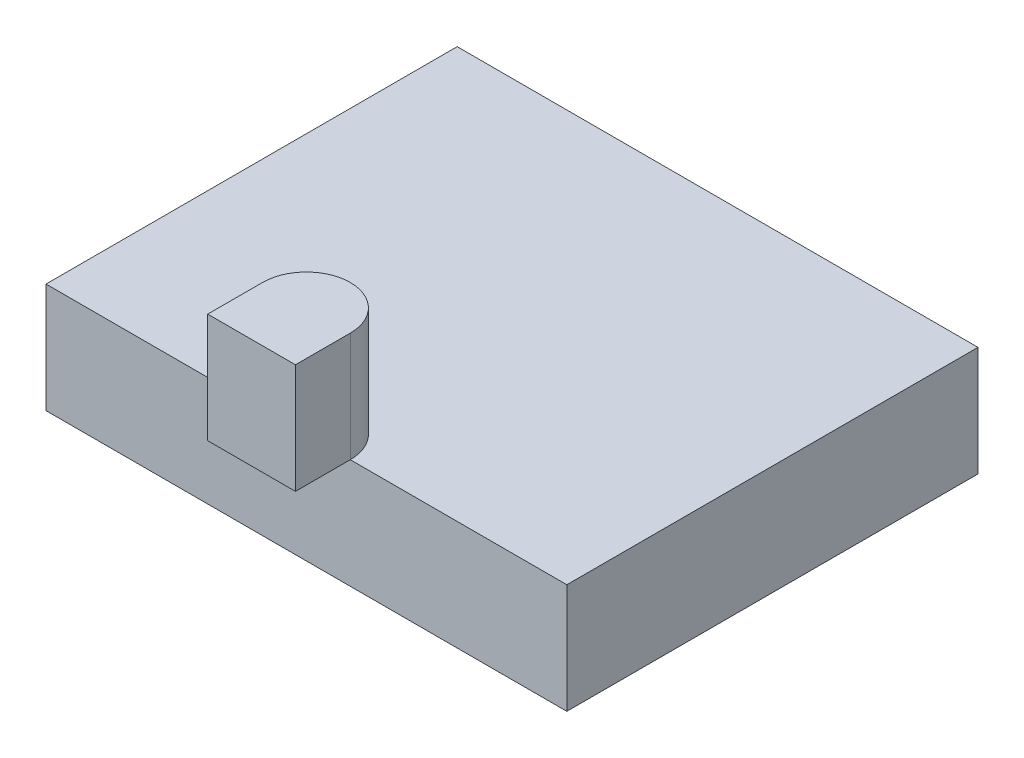
SolidWorks part; units mm, degrees
ref_plane "Front Plane" through (0, 0, 0) normal (0, 0, 1) x (1, 0, 0)
ref_plane "Top Plane" through (0, 0, 0) normal (0, 1, 0) x (1, 0, 0)
ref_plane "Right Plane" through (0, 0, 0) normal (1, 0, 0) x (0, 0, -1)
sketch "Sketch1" plane through (0, 0, 0) normal (0, 1, 0) x (1, 0, 0)
  line L1 (-47.5, 37.5) -> (47.5, 37.5)
  line L2 (-47.5, 37.5) -> (-47.5, -37.5)
  line L3 (-47.5, -37.5) -> (47.5, -37.5)
  line L4 (47.5, 37.5) -> (47.5, -37.5)
  line L5 (-47.5, 37.5) -> (47.5, -37.5) construction
  line L6 (-47.5, -37.5) -> (47.5, 37.5) construction
  point P0 (0, 0)
  dimension "D1" = 95
  dimension "D2" = 75
extrude "Boss-Extrude1" add sketch "Sketch1" along normal mid plane 20
sketch "Sketch2" plane through (0, 0, 37.5) normal (0, 0, 1) x (1, 0, 0)
  line L0 (0, 10) -> (0, 30)
  line L1 (-47.5, 10) -> (47.5, 10) construction
  line L2 (0, 30) -> (-8, 30)
  line L3 (-8, 30) -> (-8, 10)
  line L4 (-8, 10) -> (0, 10)
  dimension "D1" = 8
  dimension "D2" = 20
revolve "Revolve1" add sketch "Sketch2" angle 180 about L0 reverse direction yes
sketch "Sketch3" plane through (0, 0, 37.5) normal (0, 0, 1) x (1, 0, 0)
  line L1 (-8, 30) -> (8, 30)
  line L2 (-8, 30) -> (-8, 10)
  line L3 (-8, 10) -> (8, 10)
  line L4 (8, 30) -> (8, 10)
  line L5 (-8, 30) -> (8, 10) construction
  line L6 (-8, 10) -> (8, 30) construction
  point P4 (0, 20)
extrude "Boss-Extrude2" add sketch "Sketch3" along normal blind 10
